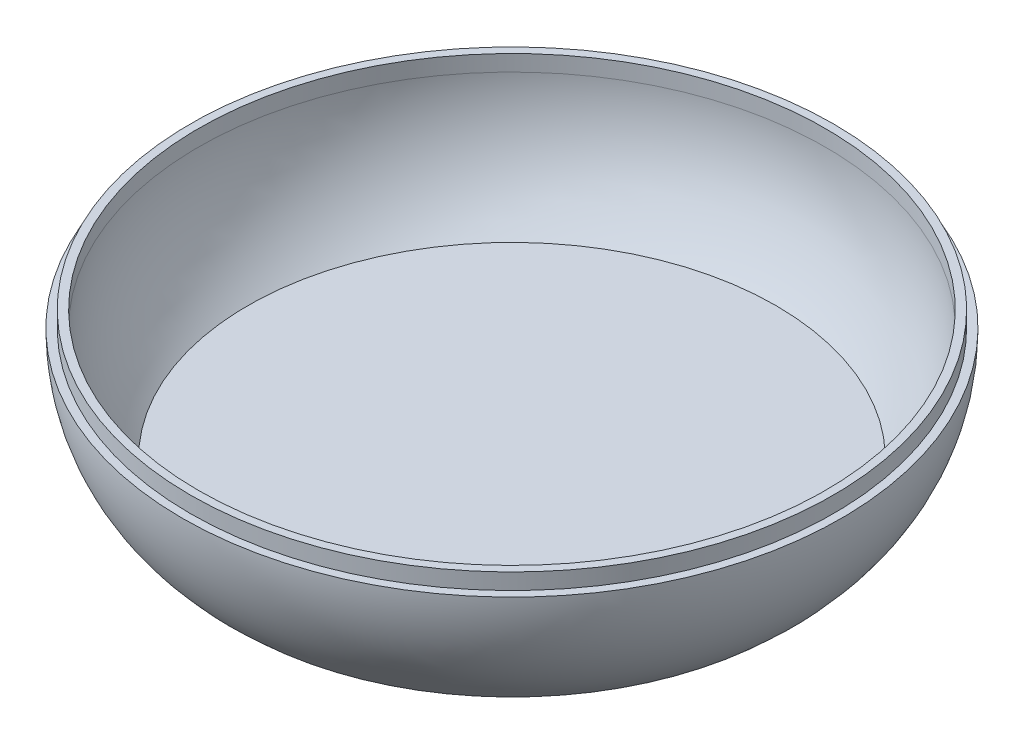
SolidWorks part; units mm, degrees
material "PE Low/Medium Density"
ref_plane "Front Plane" through (0, 0, 0) normal (0, 0, 1) x (1, 0, 0)
ref_plane "Top Plane" through (0, 0, 0) normal (0, 1, 0) x (1, 0, 0)
ref_plane "Right Plane" through (0, 0, 0) normal (1, 0, 0) x (0, 0, -1)
sketch "Sketch1"
  line L3 (0, 0) -> (41, 0)
  line L4 (7.3985, -16) -> (41, -16)
  line L7 (41, 0) -> (41, -16)
  line L8 (41, 0) -> (21, 0)
  arc A3 (0, 0) -> (7.3985, -16) centre (21, 0) ccw
sketch "Sketch1<2>" plane through (0, 0, 0) normal (0, 0, 1) x (1, 0, 0) same geometry as "Sketch1"
revolve "Revolve2" add sketch "Sketch1" angle 360 about L7
shell "Shell2" thickness 2 removed face at (41, 0, 41)
sketch "Sketch6" plane through (0, 0, 0) normal (0, 1, 0) x (1, 0, 0)
  circle A0 centre (41, 0) radius 39
  circle A1 centre (41, 0) radius 40
extrude "Boss-Extrude1" add sketch "Sketch6" along normal blind 2
